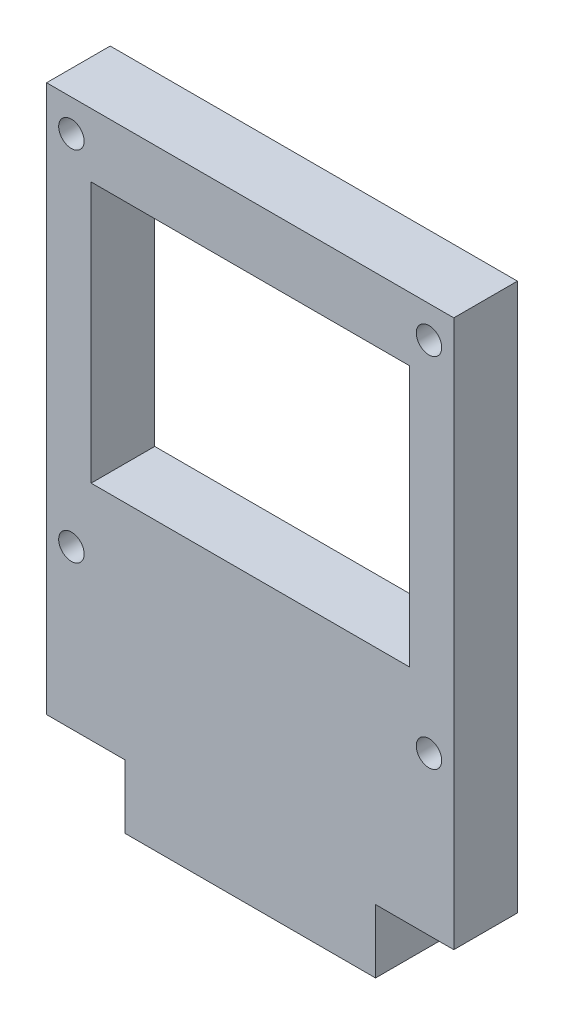
SolidWorks part; units mm, degrees
ref_plane "Front Plane" through (0, 0, 0) normal (0, 0, 1) x (1, 0, 0)
ref_plane "Top Plane" through (0, 0, 0) normal (0, 1, 0) x (1, 0, 0)
ref_plane "Right Plane" through (0, 0, 0) normal (1, 0, 0) x (0, 0, -1)
sketch "Sketch2" plane through (0, 0, 0) normal (0, 1, 0) x (1, 0, 0)
  line L1 (-9.85, 5) -> (9.85, 5)
  line L2 (-9.85, 5) -> (-9.85, 0)
  line L3 (-9.85, 0) -> (9.85, 0)
  line L4 (9.85, 5) -> (9.85, 0)
  point P12 (0, 0)
  dimension "D4" = 5
  dimension "D5" = 19.7
extrude "Boss-Extrude1" add sketch "Sketch2" along normal blind 5
sketch "Sketch4" plane through (0, 0, 0) normal (0, 0, 1) x (1, 0, 0)
  line L0 (-16, 5) -> (16, 5)
  line L2 (-16, 5) -> (-16, 48)
  line L5 (-12.5, 22.5) -> (12.5, 22.5)
  line L9 (-12.5, 22.5) -> (-12.5, 43)
  line L10 (-12.5, 43) -> (0, 43)
  line L12 (-16, 48) -> (0, 48)
  line L13 (0, 5) -> (0, 22.5) construction
  line L14 (16, 48) -> (0, 48)
  line L16 (12.5, 43) -> (0, 43)
  line L17 (12.5, 22.5) -> (12.5, 43)
  line L18 (16, 5) -> (16, 48)
  line L19 (-9.85, 5) -> (9.85, 5) construction
  dimension "D1" = 3.5
  dimension "D2" = 43
  dimension "D3" = 17.5
  dimension "D5" = 5
  dimension "D6" = 16
extrude "Boss-Extrude2" add sketch "Sketch4" against normal up to surface (5 mm away) up to face at (0, 2.5, -5)
sketch "Sketch5" plane through (0, 0, 0) normal (0, 0, 1) x (1, 0, 0)
  line L0 (0, 0) -> (0, 22.5) construction
  line L1 (-9.85, 0) -> (9.85, 0) construction
  line L2 (-12.5, 22.5) -> (12.5, 22.5) construction
  line L3 (-14.05, 44.5) -> (-14.05, 18.4) construction
  line L4 (-12.5, 43) -> (-12.5, 48) construction
  line L7 (16, 48) -> (-16, 48) construction
  circle A0 centre (-14.05, 45.5) radius 1
  circle A1 centre (-14.05, 17.4) radius 1
  circle A2 centre (14.05, 17.4) radius 1
  circle A3 centre (14.05, 45.5) radius 1
  point P12 (-12.5, 45.5)
  dimension "D2" = 2
  dimension "D1" = 26.1
  dimension "D3" = 14.05
extrude "Cut-Extrude1" cut sketch "Sketch5" against normal up to surface (5 mm away) up to face at (0, 14.5, -5)
equation "\"D3@Sketch5\"=(\"D1@Sketch5\"/2)+(\"D2@Sketch5\"/2)"
